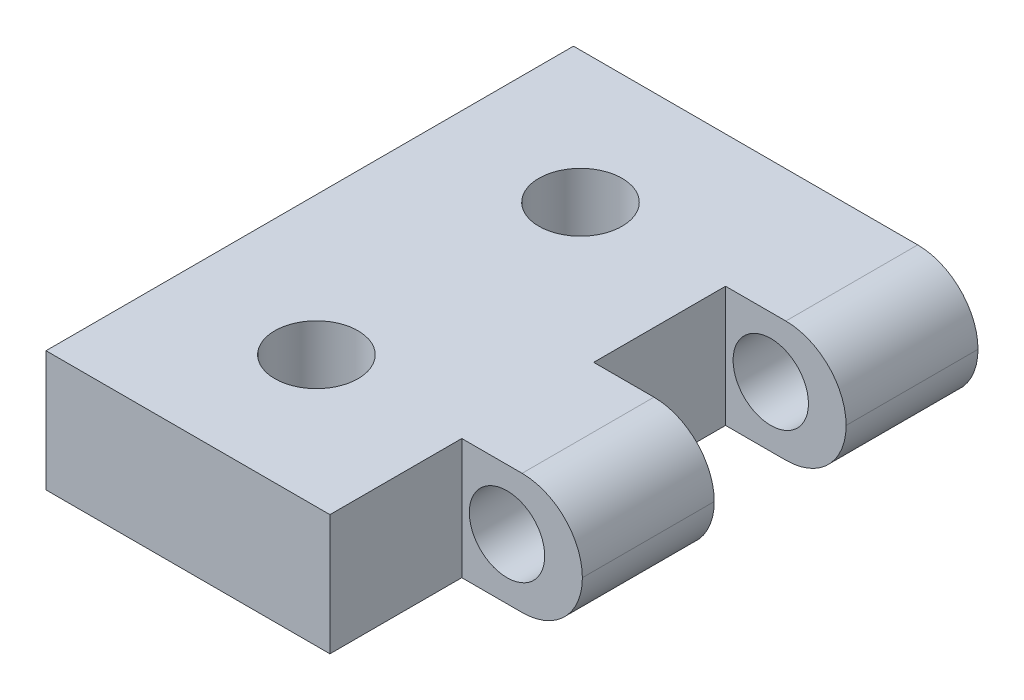
SolidWorks part; units mm, degrees
ref_plane "Front Plane" through (0, 0, 0) normal (0, 0, 1) x (1, 0, 0)
ref_plane "Top Plane" through (0, 0, 0) normal (0, 1, 0) x (1, 0, 0)
ref_plane "Right Plane" through (0, 0, 0) normal (1, 0, 0) x (0, 0, -1)
sketch "Sketch1" plane through (0, 0, 0) normal (0, 1, 0) x (1, 0, 0)
  line L1 (0, 0) -> (17.0425, 0)
  line L2 (0, 0) -> (0, 22.225)
  line L3 (0, 22.225) -> (17.0425, 22.225)
  line L4 (17.0425, 0) -> (17.0425, 22.225)
  dimension "D1" = 22.225
  dimension "D2" = 17.0425
extrude "Boss-Extrude1" add sketch "Sketch1" along normal blind 5.08
sketch "Sketch3" plane through (0, 0, 0) normal (0, 0, 1) x (1, 0, 0)
  line L3 (0, 5.08) -> (17.0425, 5.08) construction
  line L4 (17.0425, 5.08) -> (17.0425, 0) construction
  circle A0 centre (13.8675, 2.54) radius 1.5875
  point P2 (14.048, 2.5672)
  point P5 (13.8659, 2.5616)
  dimension "D1" = 3.175
  dimension "D2" = 2.54
  dimension "D3" = 3.175
extrude "Cut-Extrude1" cut sketch "Sketch3" against normal through all
fillet "Fillet1" radius 2.54 2 edges at (17.0425, 0, -11.1125) (17.0425, 5.08, -11.1125)
sketch "Sketch4" plane through (0, 5.08, 0) normal (0, 1, 0) x (1, 0, 0)
  line L0 (0, 0) -> (14.5025, 0) construction
  line L1 (11.9625, 0) -> (17.0425, 0)
  line L2 (11.9625, 0) -> (11.9625, 5.5562)
  line L3 (11.9625, 5.5562) -> (17.0425, 5.5562)
  line L4 (17.0425, 0) -> (17.0425, 5.5562)
  line L5 (17.0425, 22.225) -> (17.0425, 0) construction
  line L7 (11.9625, 11.1125) -> (17.0425, 11.1125)
  line L8 (11.9625, 11.1125) -> (11.9625, 16.6687)
  line L9 (11.9625, 16.6687) -> (17.0425, 16.6687)
  line L10 (17.0425, 11.1125) -> (17.0425, 16.6687)
  dimension "D1" = 5.5562
  dimension "D2" = 5.08
  dimension "D3" = 5.5562
  dimension "D4" = 5.5562
  dimension "D5" = 5.08
extrude "Cut-Extrude2" cut sketch "Sketch4" against normal through all
sketch "Sketch5" plane through (0, 5.08, 0) normal (0, 1, 0) x (1, 0, 0)
  line L0 (5.8434, 16.6751) -> (5.8434, 5.5499) construction
  circle A0 centre (5.8434, 16.6751) radius 1.7526
  circle A1 centre (5.8434, 5.5499) radius 1.7526
  point P4 (5.8434, 11.1125)
  dimension "D1" = 3.5052
  dimension "D2" = 3.5052
  dimension "D3" = 11.1252
extrude "Cut-Extrude3" cut sketch "Sketch5" against normal through all
